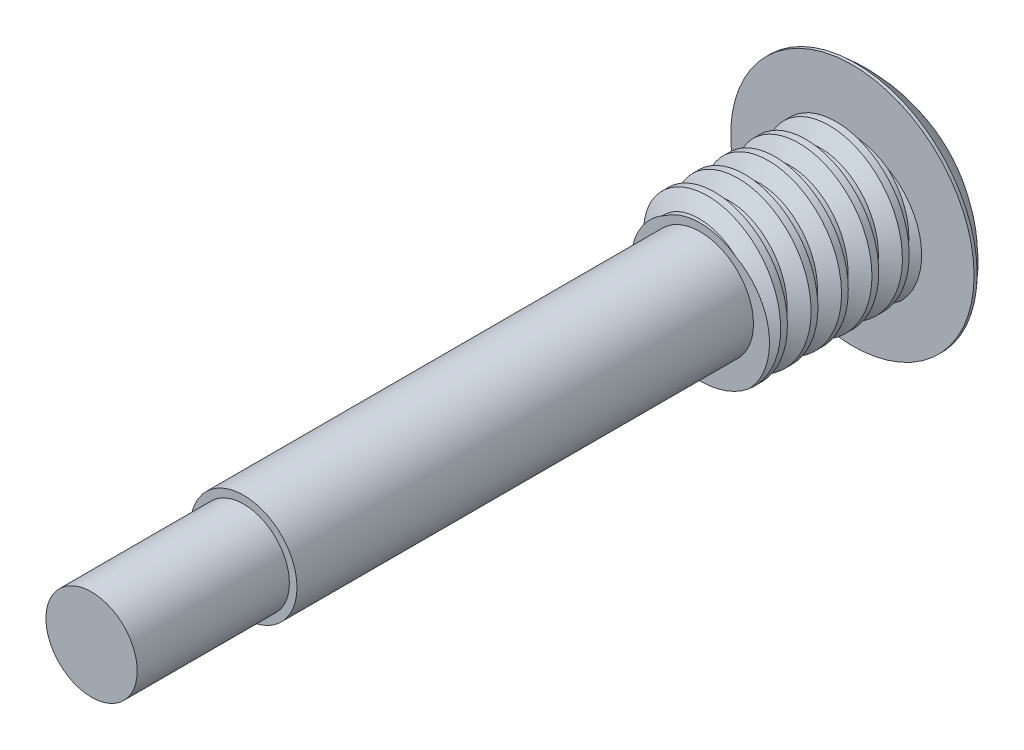
SolidWorks part; units mm, degrees
ref_plane "Front Plane" through (0, 0, 0) normal (0, 0, 1) x (1, 0, 0)
ref_plane "Top Plane" through (0, 0, 0) normal (0, 1, 0) x (1, 0, 0)
ref_plane "Right Plane" through (0, 0, 0) normal (1, 0, 0) x (0, 0, -1)
sketch "Sketch2" plane through (0, 0, 0) normal (0, 0, 1) x (1, 0, 0)
  circle A0 centre (0, 0) radius 3.175
curve "Helix/Spiral1" pitch 1.27 height 6.35 radius 3.175 left hand yes centre (0, 0, 0) axis (0, 0, 1) start towards (0, 1, 0)
sketch "Sketch3" plane through (0, 0, 0) normal (0, 0, 1) x (1, 0, 0)
  circle A0 centre (0, 0) radius 3.175
extrude "Boss-Extrude1" add sketch "Sketch3" along normal blind 6.35 contours A0
sketch "Sketch5" plane through (0, 0, 0) normal (1, 0, 0) x (0, 0, -1)
  line L0 (0.127, 2.54) -> (0.4936, 3.175)
  line L1 (0.4936, 3.175) -> (-0.4936, 3.175)
  line L2 (-0.4936, 3.175) -> (-0.127, 2.54)
  line L3 (-0.127, 2.54) -> (0.127, 2.54)
  line L4 (0, 3.175) -> (0, 2.54) construction
  point P6 (0, 0)
  point P7 (0, 0)
  point P8 (0, 0)
  point P9 (0, 0)
  point P10 (0, 0)
  dimension "D1" = 0.635
  dimension "D2" = 0.254
  dimension "D3" = 60
sweep "Cut-Sweep1" cut profiles "Sketch5" path "Helix/Spiral1" align with end faces yes
sketch "Sketch8" plane through (0, 0, 0) normal (0, 0, 1) x (1, 0, 0)
  circle A0 centre (0, 0) radius 2.2225
extrude "Boss-Extrude3" add sketch "Sketch8" along normal blind 25.4
sketch "Sketch9" plane through (0, 0, 0) normal (0, 0, 1) x (1, 0, 0)
  circle A0 centre (0, 0) radius 5.08
  dimension "D1" = 10.16
extrude "Boss-Extrude4" add sketch "Sketch9" against normal blind 0.127
dome "Dome3" faces to dome 1 distance 2.38 reverse direction no elliptical dome no face at (5.08, 0, -0.127) parameters "D1"=2.38
sketch "Sketch10" plane through (0, 0, 25.4) normal (0, 0, 1) x (1, 0, 0)
  circle A0 centre (0, 0) radius 1.905
extrude "Boss-Extrude5" add sketch "Sketch10" along normal blind 6.35
